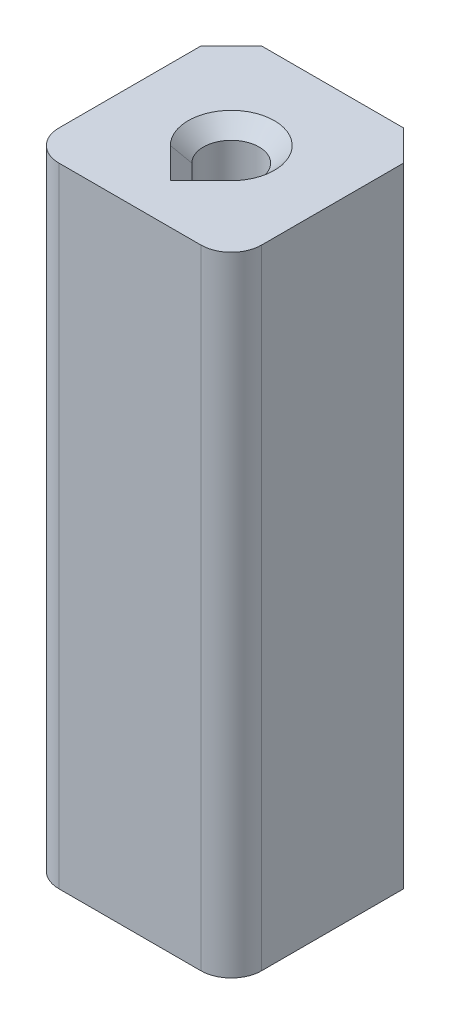
SolidWorks part; units mm, degrees
ref_plane "Front Plane" through (0, 0, 0) normal (0, 0, 1) x (1, 0, 0)
ref_plane "Top Plane" through (0, 0, 0) normal (0, 1, 0) x (1, 0, 0)
ref_plane "Right Plane" through (0, 0, 0) normal (1, 0, 0) x (0, 0, -1)
sketch "Sketch3" plane through (0, 0, 0) normal (1, 0, 0) x (0, 0, -1)
  line L0 (10, 62) -> (-10, 62)
  line L2 (-10, 62) -> (-10, 0)
  line L3 (55, 0) -> (-55, 0) construction
  line L4 (-10, 0) -> (10, 0)
  line L6 (10, 0) -> (10, 62)
  line L8 (0, 55) -> (0, -55) construction
  point P0 (0, 62)
  point P2 (15.5983, 62)
  point P4 (0, 0)
  point P8 (0, 0)
  point P12 (16, 0)
  point P13 (0, 0)
  point P14 (0, 0)
  point P15 (15.6153, 0)
  dimension "D1" = 20
  dimension "D2" = 62
extrude "Boss-Extrude1" add sketch "Sketch3" along normal blind 10 and the other way blind 10
fillet "Fillet1" radius 3 2 edges at (-10, 31, 10) (10, 31, 10)
sketch "Sketch4" plane through (0, 62, 0) normal (0, 1, 0) x (1, 0, 0)
  line L0 (0, -11) -> (0, 11) construction
  line L2 (-1.9445, -1.9445) -> (0, -3.8891)
  line L3 (0, -3.8891) -> (1.9445, -1.9445)
  circle A0 centre (0, 0) radius 2.75
  point P4 (0, 0)
  dimension "D1" = 5.5
  dimension "D3" = 45
extrude "Cut-Extrude1" cut sketch "Sketch4" against normal through all contours A0 | A0 L2 L3 region at (0, 62, 3.0204) region at (0, 62, 0)
chamfer "Chamfer1" distance 1.5 3 edges at (0.9723, 62, 2.9168) (-0.9723, 62, 2.9168) (0, 62, -2.75)
chamfer "Chamfer2" distance 3 2 edges at (-10, 31, -10) (10, 31, -10)
